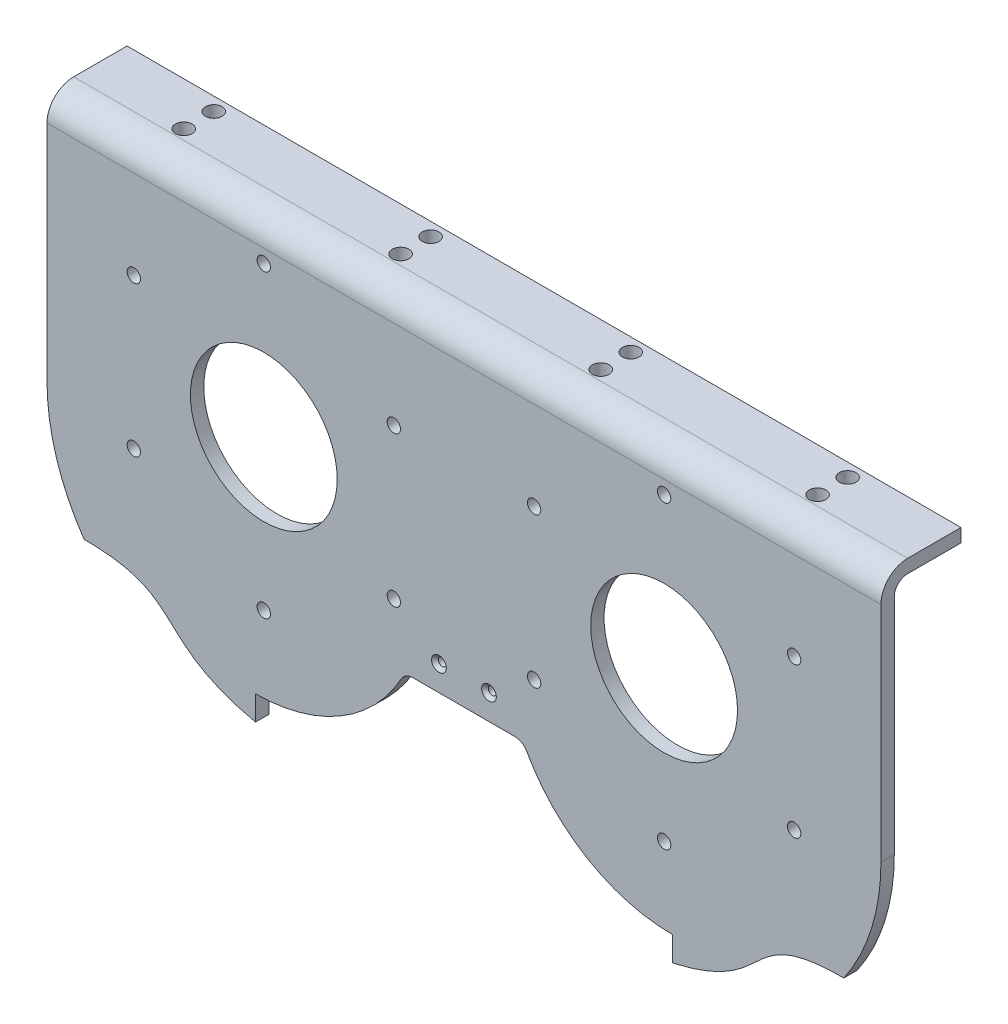
SolidWorks part; units mm, degrees
note: '?' marks a value the reader was unsure of.
material "1060 Alloy"
ref_plane "Front Plane" through (0, 0, 0) normal (0, 0, 1) x (1, 0, 0)
ref_plane "Top Plane" through (0, 0, 0) normal (0, 1, 0) x (1, 0, 0)
ref_plane "Right Plane" through (0, 0, 0) normal (1, 0, 0) x (0, 0, -1)
sketch "Sketch1" plane through (0, 0, 0) normal (0, 0, 1) x (1, 0, 0)
  line L1 (-125, 74.8569) -> (125, 74.8569)
  line L2 (-125, 74.8569) -> (-125, -80.4165)
  line L3 (-125, -80.4165) -> (125, -80.4165)
  line L4 (125, 74.8569) -> (125, -80.4165)
  dimension "D1" = 250
  dimension "D2" = 125
extrude "Boss-Extrude1" add sketch "Sketch1" along normal blind 4
ref_plane "Plane1" through (-60, 0, 0) normal (1, 0, 0) x (0, 0, -1)
ref_axis "Axis1" through (-60, 0, 54.5094) along (0, 0, -1)?
fillet "Fillet1" radius 62.5 2 edges at (125, -80.4165, 2) (-125, -80.4165, 2)
sketch "Sketch5" plane through (0, 0, 4) normal (0, 0, 1) x (1, 0, 0)
  line L2 (15.2965, -40.1431) -> (-15.2965, -40.1431)
  line L3 (125, 74.8569) -> (-125, 74.8569) construction
  line L5 (-62.5, -67.9165) -> (-62.5, -80.4165)
  line L6 (-62.5, -80.4165) -> (62.5, -80.4165)
  line L7 (62.5, -67.9165) -> (62.5, -80.4165)
  arc A0 (-62.5, -67.9165) -> (-18.7931, -42.2004) centre (-62.5, -17.9165) ccw
  arc A1 (62.5, -67.9165) -> (18.7931, -42.2004) centre (62.5, -17.9165) cw
  arc A3 (15.2965, -40.1431) -> (18.7931, -42.2004) centre (15.2965, -44.1431) cw
  arc A4 (-15.2965, -40.1431) -> (-18.7931, -42.2004) centre (-15.2965, -44.1431) ccw
  dimension "D1" = 4
  dimension "D2" = 50
  dimension "D3" = 115
  dimension "D4" = 12.5
  dimension "D5" = 12.5
extrude "Cut-Extrude1" cut sketch "Sketch5" against normal blind 10
sketch "Sketch6" plane through (0, 0, 4) normal (0, 0, 1) x (1, 0, 0)
  line L0 (-113.8719, -53.514) -> (-113.8719, -84.7363)
  line L1 (-113.8719, -84.7363) -> (-44.8214, -84.7363)
  line L2 (-44.8214, -84.7363) -> (-44.8214, -77.8642)
  arc A0 (-125, -17.9165) -> (-62.5, -80.4165) centre (-62.5, -17.9165) ccw construction
  arc A1 (-125, -17.9165) -> (-62.5, -80.4165) centre (-62.5, -17.9165) ccw construction
  spline S0 degree 3 poles (-113.8719, -53.514) (-77.9351, -53.5255) (-98.5153, -73.0801) (-44.8214, -77.8642) knots 0 0 0 0 1 1 1 1
extrude "Cut-Extrude2" cut sketch "Sketch6" against normal blind 10
mirror "Mirror2" about plane through (0, 0, 0) normal (1, 0, 0) of "Cut-Extrude2"
sketch "Sketch7" plane through (0, 0, 4) normal (0, 0, 1) x (1, 0, 0)
  line L0 (55, 0) -> (-55, 0) construction
  line L1 (-60, -44.7868) -> (-60, 44.7868) construction
  circle A0 centre (-60, 0) radius 22
  dimension "D1" = 0
extrude "Cut-Extrude3" cut sketch "Sketch7" against normal blind 7
mirror "Mirror3" about plane through (0, 0, 0) normal (1, 0, 0) of "Cut-Extrude3"
sketch "Sketch8" plane through (0, 0, 4) normal (0, 0, 1) x (1, 0, 0)
  line L0 (125, -17.9165) -> (125, 74.8569) construction
  line L1 (-125, 74.8569) -> (125, 74.8569)
  line L2 (-125, 74.8569) -> (-125, 55)
  line L3 (-125, 55) -> (125, 55)
  line L4 (125, 74.8569) -> (125, 55)
  circle A0 centre (-60, 0) radius 22 construction
  dimension "D1" = 55
extrude "Cut-Extrude4" cut sketch "Sketch8" against normal blind 7
ref_plane "Plane3" through (0, 0, 0) normal (1, 0, 0) x (0, 0, -1)
ref_plane "Plane4" through (0, 55, 0) normal (0, 1, 0) x (1, 0, 0)
sketch "Sketch9" plane through (0, 0, 0) normal (0, 0, -1) x (-1, 0, 0)
  line L0 (125, 55) -> (125, -17.9165) construction
  line L1 (-125, 55) -> (125, 55)
  line L2 (-125, 55) -> (-125, 51)
  line L3 (-125, 51) -> (125, 51)
  line L4 (125, 55) -> (125, 51)
  dimension "D1" = 4
extrude "Boss-Extrude2" [suppressed] add sketch "Sketch9" along normal blind 20
sketch "Sketch10" [suppressed] plane through (125, 0, 0) normal (1, 0, 0) x (0, 0, -1)
  line L0 (10, 51) -> (0, 41)
  line L1 (20, 51) -> (0, 51) construction
  line L2 (0, -17.9165) -> (0, 51) construction
  line L3 (0, 41) -> (0, 51)
  line L4 (0, 51) -> (10, 51)
  dimension "D1" = 315
extrude "Boss-Extrude3" [suppressed] add sketch "Sketch10" against normal blind 5
fillet "Fillet2" [suppressed] radius 5
mirror "Mirror4" [suppressed] about plane through (0, 0, 0) normal (1, 0, 0)
sketch "Sketch13" [suppressed] plane through (0, 0, 0) normal (1, 0, 0) x (0, 0, -1)
  line L0 (0, 51) -> (0, 41)
  line L1 (0, 41) -> (10, 51)
  line L3 (0, 51) -> (10, 51)
  line L5 (0, 51) -> (0, 38.9289) construction
  line L6 (12.0711, 51) -> (0, 51) construction
  dimension "D1" = 45
  dimension "D2" = 10
extrude "Boss-Extrude4" [suppressed] add sketch "Sketch13" along normal mid plane 20
fillet "Fillet3" [suppressed] radius 5
hole_wizard "Ø5.0 (5) Diameter Hole1" [suppressed] positions "Sketch14" profile "Sketch15" hole size "Ø5.0" standard "ISO"
sketch "Sketch14" [suppressed] plane through (0, 55, 0) normal (0, 1, 0) x (1, 0, 0)
  line L2 (-125, -4) -> (125, -4) construction
  line L4 (-125, 1.4645) -> (-125, 8.5355) construction
  line L5 (-125, 20) -> (-125, -4) construction
  point P0 (-95, 15)
  point P2 (-95, 6)
  dimension "D1" = 30
  dimension "D2" = 30
  dimension "D3" = 9
  dimension "D4" = 10
sketch "Sketch15" plane through (-95, 55, -15) normal (1, 0, 0) x (0, 0, 1)
  line L0 (0, 0) -> (0, 51.5022)
  line L1 (0, 51.5022) -> (2.5, 50)
  line L2 (2.5, 50) -> (2.5, 0)
  line L5 (2.5, 0) -> (0, 0)
  line L10 (0, 51.5022) -> (-2.5, 50) construction
  line L11 (0, -6.35) -> (0, 107.95) construction
  dimension "Hole Dia." = 5
  dimension "Hole Depth" = 50
  dimension "Drill Angle" = 118
pattern_linear "LPattern1" [suppressed] count 2 spacing 65
mirror "Mirror5" [suppressed] about plane through (0, 0, 0) normal (1, 0, 0)
sketch "Sketch17" plane through (0, 0, 0) normal (1, 0, 0) x (0, 0, -1)
  line L0 (0, -40.1431) -> (0, -25.1431)
  line L1 (0, -53.514) -> (0, -17.9165) construction
  line L3 (15, -40.1431) -> (0, -40.1431)
  line L9 (15, -25.1431) -> (0, -25.1431)
  line L10 (15, -25.1431) -> (15, -40.1431)
  dimension "D1" = 15
  dimension "D2" = 15
extrude "Boss-Extrude5" [suppressed] add sketch "Sketch17" along normal mid plane 30 separate body
hole_wizard "M5 Tapped Hole1" [suppressed] positions "Sketch18" profile "Sketch19" tap size "M5" standard "ISO"
sketch "Sketch18" [suppressed] plane through (0, -40.1431, 0) normal (0, 1, 0) x (1, 0, 0)
  line L0 (0, -20.2479) -> (0, 20.2479) construction
  line L3 (15, 15) -> (-15, 15) construction
  point P0 (-7.5, 8.75)
  point P2 (7.5, 8.75)
  dimension "D1" = 7.5
  dimension "D2" = 7.5
  dimension "D4" = 0
  dimension "D3" = 6.25
sketch "Sketch19" plane through (-7.5, -40.1431, -8.75) normal (1, 0, 0) x (0, 0, -1)
  line L0 (0, 0) -> (0, 13.6618)
  line L1 (0, 13.6618) -> (2.1, 12.4)
  line L2 (2.1, 12.4) -> (2.1, 0)
  line L5 (2.1, 0) -> (0, 0)
  line L10 (0, 13.6618) -> (-2.1, 12.4) construction
  line L11 (0, -6.35) -> (0, 107.95) construction
  dimension "Tap Drill Dia." = 4.2
  dimension "Tap Drill Depth" = 12.4
  dimension "Drill Angle" = 118
fillet "Fillet4" [suppressed] radius 2.5
sketch "Sketch20" plane through (-125, 0, 0) normal (-1, 0, 0) x (0, 0, 1)
  line L0 (4, 45.2816) -> (0, 45.2816)
  line L1 (4, 55) -> (4, -17.9165) construction
  line L2 (0, 55) -> (0, -17.9165) construction
  line L3 (0, 45.2816) -> (0, 49.0035)
  line L4 (-4, 53.0035) -> (-20, 53.0035)
  line L5 (-20, 53.0035) -> (-20, 57.0035)
  line L6 (-20, 57.0035) -> (-4, 57.0035)
  line L7 (4, 49.0035) -> (4, 45.2816)
  line L8 (0, -17.9165) -> (4, -17.9165) construction
  arc A0 (-4, 57.0035) -> (4, 49.0035) centre (-4, 49.0035) cw
  arc A1 (0, 49.0035) -> (-4, 53.0035) centre (-4, 49.0035) ccw
  dimension "D2" = 8
  dimension "D3" = 4
  dimension "D1" = 4
  dimension "D4" = 74.92
extrude "Boss-Extrude6" add sketch "Sketch20" against normal up to surface (250 mm away) up to face at (125, 18.5417, 2)
sketch "Sketch22" plane through (-125, 0, 0) normal (-1, 0, 0) x (0, 0, 1)
  line L1 (1.2954, 55) -> (4, 55) construction
  line L3 (1.2954, 55) -> (4, 55)
  line L6 (4, 55) -> (4, -17.9165) construction
  line L7 (4, 49.0035) -> (4, 55)
  arc A1 (1.2954, 55) -> (4, 49.0035) centre (-4, 49.0035) cw
extrude "Cut-Extrude6" cut sketch "Sketch22" against normal up to surface (250 mm away) up to face at (125, 38.2774, -4.1881)
hole_wizard "Ø4.0mm Dowel Hole1" positions "Sketch2" profile "Sketch3" hole size "Ø4.0" standard "ISO"
sketch "Sketch2" plane through (0, 0, 4) normal (0, 0, 1) x (1, 0, 0)
  line L0 (0, -44.7868) -> (0, 44.7868) construction
  line L1 (55, 0) -> (-55, 0) construction
  point P0 (-60, 45)
  dimension "D1" = 60
  dimension "D2" = 45
sketch "Sketch3" plane through (-60, 45, 4) normal (1, 0, 0) x (0, -1, 0)
  line L0 (0, 0) -> (0, 51.2017)
  line L1 (0, 51.2017) -> (2, 50)
  line L2 (2, 50) -> (2, 0)
  line L5 (2, 0) -> (0, 0)
  line L10 (0, 51.2017) -> (-2, 50) construction
  line L11 (0, -6.35) -> (0, 107.95) construction
  dimension "Hole Dia." = 4
  dimension "Hole Depth" = 50
  dimension "Drill Angle" = 118
pattern_circular "CirPattern1" count 6 over 360 about axis through (-60, 0, 0) along (0, 0, 1) of "Ø4.0mm Dowel Hole1"
mirror "Mirror1" about plane through (0, 0, 0) normal (1, 0, 0) of "CirPattern1", "Ø4.0mm Dowel Hole1"
hole_wizard "Ø5.0 (5) Diameter Hole2" positions "Sketch23" profile "Sketch24" hole size "Ø5.0" standard "ISO"
sketch "Sketch23" plane through (0, 57.0035, 0) normal (0, 1, 0) x (1, 0, 0)
  line L0 (-125, 4) -> (-125, 20) construction
  line L1 (125, -4) -> (-125, -4) construction
  point P0 (-95, 16)
  point P2 (-95, 7)
  dimension "D1" = 30
  dimension "D2" = 0
  dimension "D3" = 11
  dimension "D4" = 9
sketch "Sketch24" plane through (-95, 57.0035, -16) normal (1, 0, 0) x (0, 0, 1)
  line L0 (0, 0) -> (0, 51.5022)
  line L1 (0, 51.5022) -> (2.5, 50)
  line L2 (2.5, 50) -> (2.5, 0)
  line L5 (2.5, 0) -> (0, 0)
  line L10 (0, 51.5022) -> (-2.5, 50) construction
  line L11 (0, -6.35) -> (0, 107.95) construction
  dimension "Hole Dia." = 5
  dimension "Hole Depth" = 50
  dimension "Drill Angle" = 118
pattern_linear "LPattern2" count 2 spacing 65 along (1, 0, 0) of "Ø5.0 (5) Diameter Hole2"
mirror "Mirror6" about plane through (0, 0, 0) normal (1, 0, 0) of "LPattern2", "Ø5.0 (5) Diameter Hole2"
fillet "Fillet5" [suppressed] radius 2.5
hole_wizard "CSK for M2 Countersunk Flat Head Screw1" positions "Sketch27" profile "Sketch26" countersink size "M2" standard "ISO"
sketch "Sketch27" plane through (0, 0, 4) normal (0, 0, 1) x (1, 0, 0)
  line L0 (0, -20.2479) -> (0, 20.2479) construction
  line L1 (15.2965, -40.1431) -> (-15.2965, -40.1431) construction
  point P0 (-7.5, -32.6431)
  point P2 (7.5, -32.6431)
  dimension "D1" = 7.5
  dimension "D2" = 7.5
  dimension "D3" = 7.5
  dimension "D4" = 0
sketch "Sketch26" plane through (-7.5, -32.6431, 4) normal (1, 0, 0) x (0, -1, 0)
  line L0 (0, 0) -> (0, 9.721)
  line L1 (0, 9.721) -> (1.2, 9)
  line L2 (1.2, 9) -> (1.2, 1)
  line L3 (1.2, 1) -> (2.2, 0)
  line L5 (2.2, 0) -> (0, 0)
  line L6 (-1.2, 1) -> (-2.2, 0) construction
  line L10 (0, 9.721) -> (-1.2, 9) construction
  line L11 (0, -6.35) -> (0, 107.95) construction
  dimension "Hole Dia." = 2.4
  dimension "Hole Depth" = 9
  dimension "Near C'Sink Dia." = 4.4
  dimension "Near C'Sink Angle" = 90
  dimension "Drill Angle" = 118
equation "\"Supportwidth\"=30"
equation "\"D1@Boss-Extrude5\"=\"Supportwidth\""
equation "\"D1@Sketch18\"=\"Supportwidth\"/4"
equation "\"D2@Sketch18\"=\"Supportwidth\"/4"
equation "\"Supportlength\"=15"
equation "\"D1@Sketch17\"=\"Supportlength\""
equation "\"TopLength\"=20"
equation "\"D1@Boss-Extrude2\"=\"TopLength\""
